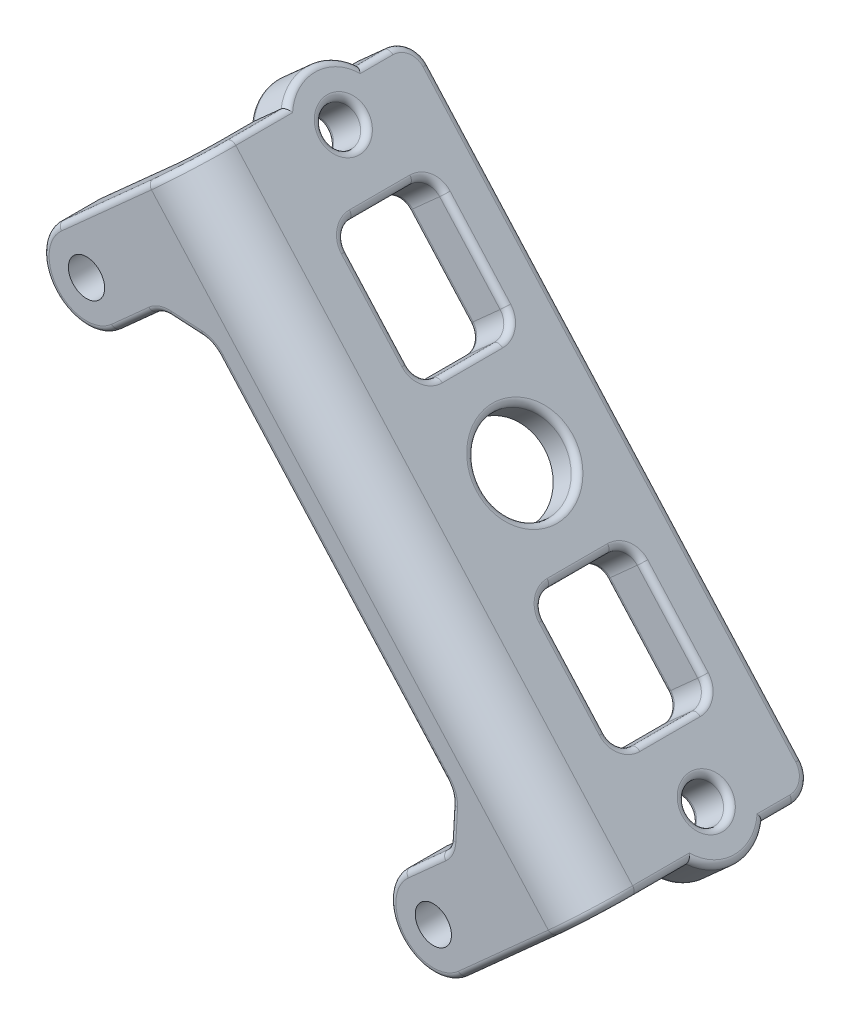
SolidWorks part; units mm, degrees
material "尼龙 101"
ref_plane "前视基准面" through (0, 0, 0) normal (0, 0, 1) x (1, 0, 0)
ref_plane "上视基准面" through (0, 0, 0) normal (0, 1, 0) x (1, 0, 0)
ref_plane "右视基准面" through (0, 0, 0) normal (1, 0, 0) x (0, 0, -1)
sketch "草图1" plane through (0, 0, 0) normal (0, 0, 1) x (1, 0, 0)
  line L0 (-38.4725, -25.353) -> (-48.8943, -34.6957)
  line L1 (-51.2974, -32.0151) -> (-80, 0.003) construction
  line L2 (-65.6487, -16.006) -> (-48.8943, -0.9866) construction
  line L3 (-53.7004, -29.3345) -> (-49.98, -25.9994)
  line L4 (-49.7487, -21.763) -> (-69.6403, 0.4263)
  line L5 (-49.98, -25.9994) -> (-49.7487, -21.763)
  line L6 (-38.4725, -25.353) -> (-71.9812, 12.0263)
  line L7 (-77.597, -2.6776) -> (-73.8766, 0.6576)
  line L8 (-73.8766, 0.6576) -> (-69.6403, 0.4263)
  line L9 (-71.9812, 12.0263) -> (-82.403, 2.6836)
  circle A2 centre (-80, 0.003) radius 1.5 construction
  circle A3 centre (-51.2974, -32.0151) radius 1.5 construction
  circle A4 centre (-80, 0.003) radius 1.5
  circle A5 centre (-51.2974, -32.0151) radius 1.5
  arc A6 (-48.8943, -34.6957) -> (-53.7004, -29.3345) centre (-51.2974, -32.0151) cw
  arc A7 (-82.403, 2.6836) -> (-77.597, -2.6776) centre (-80, 0.003) ccw
  point P13 (-65.6487, -16.006)
  point P18 (-47.7462, -23.9968)
  point P24 (-59.6945, -10.6684)
  point P25 (-55.2268, -6.6634)
  dimension "D1" = 3.6
  dimension "D2" = 6
extrude "凸台-拉伸1" add sketch "草图1" along normal blind 4
fillet "圆角1" radius 2 4 edges at (-49.98, -25.9994, 2) (-49.7487, -21.763, 2) (-69.6403, 0.4263, 2) (-73.8766, 0.6576, 2)
sketch "草图2" plane through (0, 0, 4) normal (0, 0, 1) x (1, 0, 0)
  line L0 (-71.9812, 12.0263) -> (-38.4725, -25.353)
  line L1 (-71.9812, 12.0263) -> (-74.9596, 9.3562)
  line L2 (-38.4725, -25.353) -> (-41.4509, -28.023)
  line L3 (-74.9596, 9.3562) -> (-41.4509, -28.023)
  line L4 (-71.9812, 12.0263) -> (-41.4509, -28.023) construction
  line L5 (-38.4725, -25.353) -> (-74.9596, 9.3562) construction
  point P1 (-56.716, -7.9984)
  dimension "D1" = 4
extrude "凸台-拉伸2" add sketch "草图2" against normal blind 19
fillet "圆角2" radius 4 1 edges at (-55.2268, -6.6634, 4)
fillet "圆角3" radius 2 1 edges at (-58.2053, -9.3334, 0) second distance 1.75 first distance on face at (-58.2053, -9.3334, -7.5)
sketch "草图3" plane through (-33.9318, -30.4182, 0) normal (0.7446, 0.6675, 0) x (0, 0, -1)
  line L0 (7.5, 54.4025) -> (7.5, 9.4025) construction
  line L1 (15, 31.9025) -> (7.5, 31.9025) construction
  line L2 (15, 6.8025) -> (15, 57.0025) construction
  line L3 (5, 38.9025) -> (10, 38.9025)
  line L4 (3.5, 40.4025) -> (3.5, 47.9025)
  line L5 (11.5, 40.4025) -> (11.5, 47.9025)
  line L6 (5, 49.4025) -> (10, 49.4025)
  line L7 (3.5, 38.9025) -> (11.5, 49.4025) construction
  line L8 (11.5, 38.9025) -> (3.5, 49.4025) construction
  line L9 (0, 57.0025) -> (15, 57.0025) construction
  line L10 (11.5, 23.4025) -> (11.5, 15.9025)
  line L11 (5, 14.4025) -> (10, 14.4025)
  line L12 (3.5, 23.4025) -> (3.5, 15.9025)
  line L13 (5, 24.9025) -> (10, 24.9025)
  circle A0 centre (7.5, 54.4025) radius 1.5
  circle A1 centre (7.5, 9.4025) radius 1.5
  circle A2 centre (7.5, 31.9025) radius 3.5
  arc A3 (3.5, 47.9025) -> (5, 49.4025) centre (5, 47.9025) cw
  arc A4 (3.5, 40.4025) -> (5, 38.9025) centre (5, 40.4025) ccw
  arc A5 (10, 38.9025) -> (11.5, 40.4025) centre (10, 40.4025) ccw
  arc A6 (11.5, 47.9025) -> (10, 49.4025) centre (10, 47.9025) ccw
  arc A7 (11.5, 15.9025) -> (10, 14.4025) centre (10, 15.9025) cw
  arc A8 (3.5, 15.9025) -> (5, 14.4025) centre (5, 15.9025) ccw
  arc A9 (3.5, 23.4025) -> (5, 24.9025) centre (5, 23.4025) cw
  arc A10 (10, 24.9025) -> (11.5, 23.4025) centre (10, 23.4025) cw
  point P10 (7.5, 44.1525)
  dimension "D3" = 3
  dimension "D4" = 7
  dimension "D5" = 5
  dimension "D6" = 7
  dimension "D8" = 1.5
  dimension "D1" = 7.5
  dimension "D2" = 45
  dimension "D7" = 3.5
extrude "切除-拉伸1" cut sketch "草图3" against normal through all both and the other way through all
sketch "草图4" plane through (-33.9318, -30.4182, 0) normal (0.7446, 0.6675, 0) x (0, 0, -1)
  circle A0 centre (7.5, 54.4025) radius 4
  circle A1 centre (7.5, 9.4025) radius 1.5
  circle A2 centre (7.5, 9.4025) radius 1.5
  circle A3 centre (7.5, 54.4025) radius 1.5
  circle A4 centre (7.5, 54.4025) radius 1.5
  circle A5 centre (7.5, 9.4025) radius 4
  dimension "D3" = 8
  dimension "D1" = 0
  dimension "D2" = 0
extrude "凸台-拉伸3" add sketch "草图4" against normal up to surface (4 mm away) up to face at (-72.2228, 6.3034, -7.5)
fillet "圆角4" radius 2 2 edges at (-39.9617, -26.688, -15) (-73.4704, 10.6913, -15)
chamfer "倒角1" distance 1.5 angle 45 1 edges at (-55.869, -11.9395, -7.5)
fillet "圆角5" radius 0.5 86 edges at (-82.6806, -2.4, 0) (-76.0452, -1.2865, 0) (-73.8219, 0.5021, 0) (-71.7584, 0.5419, 0) (-69.7115, 0.2777, 0) (-49.9041, -21.8177, 0) (-49.8643, -23.8812, 0) (-50.1286, -25.9281, 0) (-52.1486, -27.9434, 0) (-53.9779, -34.4181, 0) (-39.3449, -26.135, 2.8284) (-45.1726, -31.3593, 4) (-53.9779, -34.4181, 4) (-52.1486, -27.9434, 4) (-50.1286, -25.9281, 4) (-49.8643, -23.8812, 4) (-49.9041, -21.8177, 4) (-59.6945, -10.6684, 4) (-69.7115, 0.2777, 4) (-71.7584, 0.5419, 4) (-73.8219, 0.5021, 4) (-76.0452, -1.2865, 4) (-82.6806, -2.4, 4) (-78.6813, 6.0199, 4) (-72.8535, 11.2442, 2.8284) (-42.1852, -27.2039, -7.5) (-72.2228, 6.3034, -7.5) (-74.5686, 8.9201, -14.4142) (-75.8941, 10.3987, -7.5) (-40.5164, -29.0655, -7.5) (-41.8419, -27.5868, -14.4142) (-58.2053, -9.3334, -15) (-54.8677, -13.0564, -7.5) (-39.2067, -24.5339, -7.5) (-69.2444, 8.9734, -7.5) (-37.538, -26.3954, -7.5) (-38.4725, -25.353, -2.2301) (-71.9812, 12.0263, -2.2301) (-72.9157, 13.0687, -7.5) (-71.9812, 12.0263, -11.7699) (-71.5901, 11.5901, -14.4142) (-55.2268, -6.6634, -15) (-38.8635, -24.9168, -14.4142) (-38.4725, -25.353, -11.7699) (-52.8906, -9.2695, -7.5) (-59.6945, -10.6684, 0) (-69.8866, 3.6972, -7.5) (-69.5933, 3.3701, -11.0607) (-66.3822, -0.2119, -11.5) (-63.171, -3.794, -11.0607) (-62.8778, -4.1211, -7.5) (-63.171, -3.794, -3.9393) (-66.3822, -0.2119, -3.5) (-69.5933, 3.3701, -3.9393) (-50.0283, -18.4548, -11.5) (-46.8172, -22.0369, -11.0607) (-46.5239, -22.364, -7.5) (-46.8172, -22.0369, -3.9393) (-50.0283, -18.4548, -3.5) (-53.2395, -14.8728, -3.9393) (-53.5327, -14.5456, -7.5) (-53.2395, -14.8728, -11.0607) (-60.1926, -1.124, -3.9393) (-59.8993, -1.4511, -7.5) (-60.1926, -1.124, -11.0607) (-63.4037, 2.4581, -11.5) (-66.6149, 6.0401, -11.0607) (-66.9081, 6.3673, -7.5) (-66.6149, 6.0401, -3.9393) (-63.4037, 2.4581, -3.5) (-50.261, -12.2027, -3.9393) (-47.0499, -15.7848, -3.5) (-43.8388, -19.3668, -3.9393) (-43.5455, -19.694, -7.5) (-43.8388, -19.3668, -11.0607) (-47.0499, -15.7848, -11.5) (-50.261, -12.2027, -11.0607) (-50.5543, -11.8756, -7.5)
